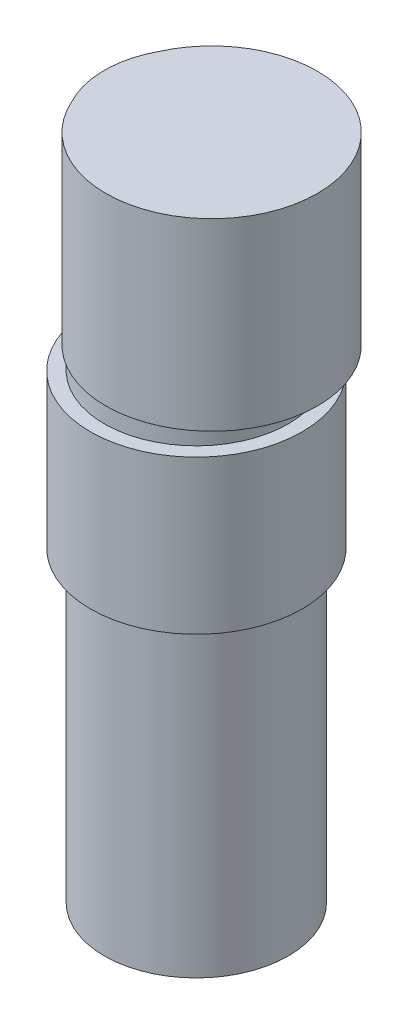
SolidWorks part; units mm, degrees
ref_plane "Front Plane" through (0, 0, 0) normal (0, 0, 1) x (1, 0, 0)
ref_plane "Top Plane" through (0, 0, 0) normal (0, 1, 0) x (1, 0, 0)
ref_plane "Right Plane" through (0, 0, 0) normal (1, 0, 0) x (0, 0, -1)
sketch "Sketch1" plane through (0, 0, 0) normal (0, 1, 0) x (1, 0, 0)
  circle A0 centre (0, 0) radius 3.45
  dimension "D1" = 6.9
extrude "Boss-Extrude1" add sketch "Sketch1" along normal blind 6
sketch "Sketch2" plane through (0, -4.98, 0) normal (0, -1, 0) x (1, 0, 0)
  line L0 (0, 0) -> (-0.5, 0) construction
  circle A0 centre (-0.5, 0) radius 3.45
  dimension "D1" = 6.9
extrude "Boss-Extrude2" add sketch "Sketch2" against normal blind 4 and the other way blind 1
sketch "Sketch3" plane through (0, 6, 0) normal (0, 1, 0) x (1, 0, 0)
  circle A0 centre (-0.5, 0) radius 3
  dimension "D1" = 6
extrude "Boss-Extrude4" add sketch "Sketch3" against normal blind 22
